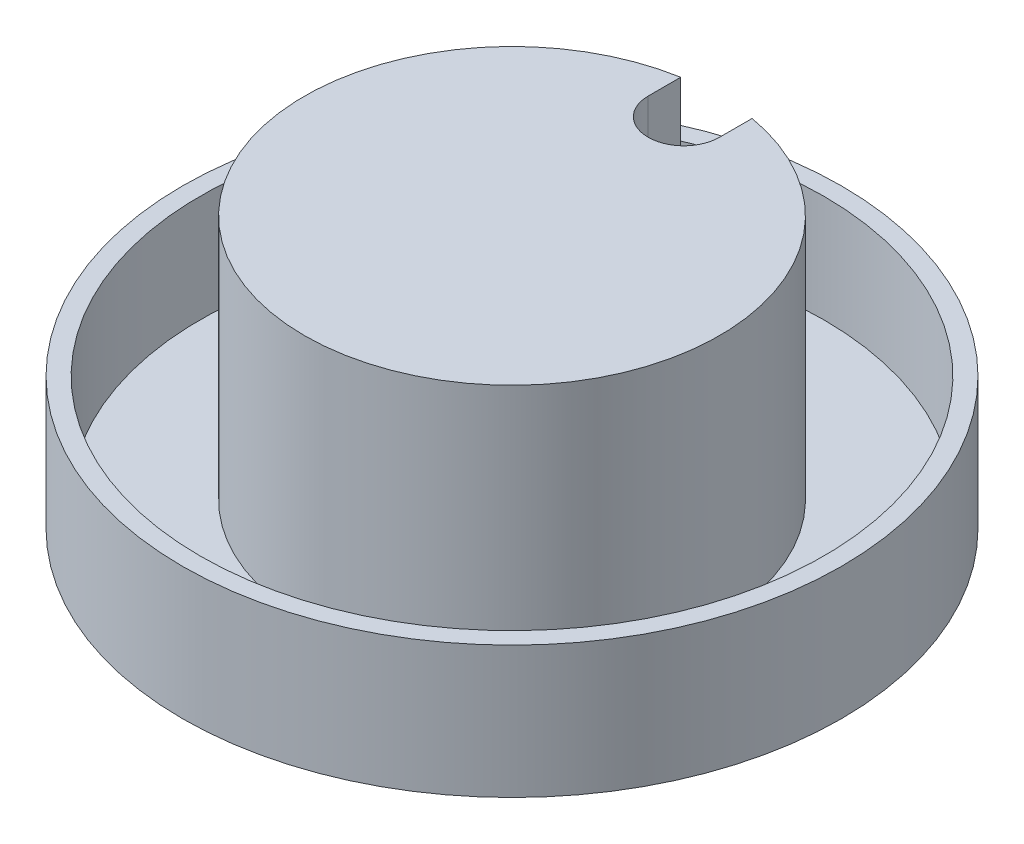
SolidWorks part; units mm, degrees
ref_plane "Front Plane" through (0, 0, 0) normal (0, 0, 1) x (1, 0, 0)
ref_plane "Top Plane" through (0, 0, 0) normal (0, 1, 0) x (1, 0, 0)
ref_plane "Right Plane" through (0, 0, 0) normal (1, 0, 0) x (0, 0, -1)
sketch "Sketch1" plane through (0, 0, 0) normal (0, 1, 0) x (1, 0, 0)
  circle A0 centre (0, 0) radius 19.85
  circle A1 centre (0, 0) radius 18.78
  circle A2 centre (0, 0) radius 12.5
  dimension "D1" = 39.7
  dimension "D2" = 1.07
  dimension "D3" = 25
extrude "Boss-Extrude3" add sketch "Sketch1" along normal blind 7.95 contours A0 | A1
sketch "Sketch2" plane through (0, 0, 0) normal (0, -1, 0) x (1, 0, 0)
  circle A0 centre (0, 0) radius 18.78
extrude "Boss-Extrude5" add sketch "Sketch2" against normal blind 1.5
sketch "Sketch4" plane through (0, 0, 0) normal (0, -1, 0) x (1, 0, 0)
  circle A0 centre (0, 0) radius 12.5
extrude "Boss-Extrude6" add sketch "Sketch4" against normal blind 16.31 separate body
sketch "Sketch5" plane through (0, 16.31, 0) normal (0, 1, 0) x (1, 0, 0)
  line L1 (2.15, 10.35) -> (-2.15, 10.35)
  line L2 (2.15, 10.35) -> (2.15, 12.5)
  line L3 (2.15, 12.5) -> (-2.15, 12.5)
  line L4 (-2.15, 10.35) -> (-2.15, 12.5)
  circle A2 centre (0, 10.35) radius 2.15
extrude "Cut-Extrude2" cut sketch "Sketch5" against normal blind 16.31 contours L2 L3 L4 L1 | A2
sketch "Sketch6" plane through (0, 0, 0) normal (0, -1, 0) x (1, 0, 0)
  circle A0 centre (0, 0) radius 11.5974
extrude "Cut-Extrude3" cut sketch "Sketch6" against normal blind 14.81
sketch "Sketch12" plane through (0, 16.31, 0) normal (0, 1, 0) x (1, 0, 0)
  line L1 (3.4, 10.35) -> (-3.4, 10.35)
  line L2 (3.4, 10.35) -> (3.4, 13.75)
  line L3 (3.4, 13.75) -> (-3.4, 13.75)
  line L4 (-3.4, 10.35) -> (-3.4, 13.75)
  circle A0 centre (0, 10.35) radius 3.4
  arc A1 (-2.15, 10.35) -> (2.15, 10.35) centre (0, 10.35) ccw construction
  dimension "D1" = 1.25
extrude "Boss-Extrude8" add sketch "Sketch12" against normal blind 24.97 contours L2 L3 L4 L1 | A0
extrude "Cut-Extrude5" cut sketch "Sketch5<6>" against normal blind 24.97 contours L1 A2 | L3 L4 L1 L2 region at (0, 16.31, -9.4375)
sketch "Sketch5<6>" plane through (0, 16.31, 0) normal (0, 1, 0) x (1, 0, 0) same geometry as "Sketch5"
sketch "Sketch14" plane through (0, 16.31, 0) normal (0, 1, 0) x (1, 0, 0)
  circle A0 centre (0, 0) radius 12.5
  circle A1 centre (0, 0) radius 15.2193
extrude "Cut-Extrude6" cut sketch "Sketch14" against normal up to vertex (14.81 mm away) up to point (3.4, 1.5, -12.0287)
sketch "Sketch17" plane through (0, 0, 0) normal (0, -1, 0) x (1, 0, 0)
  line L1 (3.4, -11.0878) -> (-3.4, -11.0878)
  line L2 (3.4, -11.0878) -> (3.4, -13.75)
  line L3 (3.4, -13.75) -> (-3.4, -13.75)
  line L4 (-3.4, -11.0878) -> (-3.4, -13.75)
extrude "Cut-Extrude7" cut sketch "Sketch17" along normal blind 16.588
sketch "Sketch18" plane through (0, 0, 0) normal (0, -1, 0) x (1, 0, 0)
  circle A0 centre (0, -10.35) radius 2.15
  circle A1 centre (0, -10.35) radius 3.4
  arc A2 (2.15, -10.35) -> (-2.15, -10.35) centre (0, -10.35) ccw construction
  arc A3 (3.4, -10.35) -> (-3.4, -10.35) centre (0, -10.35) ccw construction
  dimension "D1" = 0
  dimension "D2" = 0
extrude "Boss-Extrude10" add sketch "Sketch18" along normal blind 14
sketch "Sketch19" plane through (0, 0, 0) normal (0, -1, 0) x (1, 0, 0)
  circle A0 centre (0, -10.35) radius 3.4
  circle A1 centre (0, -10.35) radius 5.6182
  arc A2 (-3.319, -11.0878) -> (3.319, -11.0878) centre (0, -10.35) ccw construction
  dimension "D1" = 0
extrude "Cut-Extrude8" cut sketch "Sketch19" along normal blind 14
